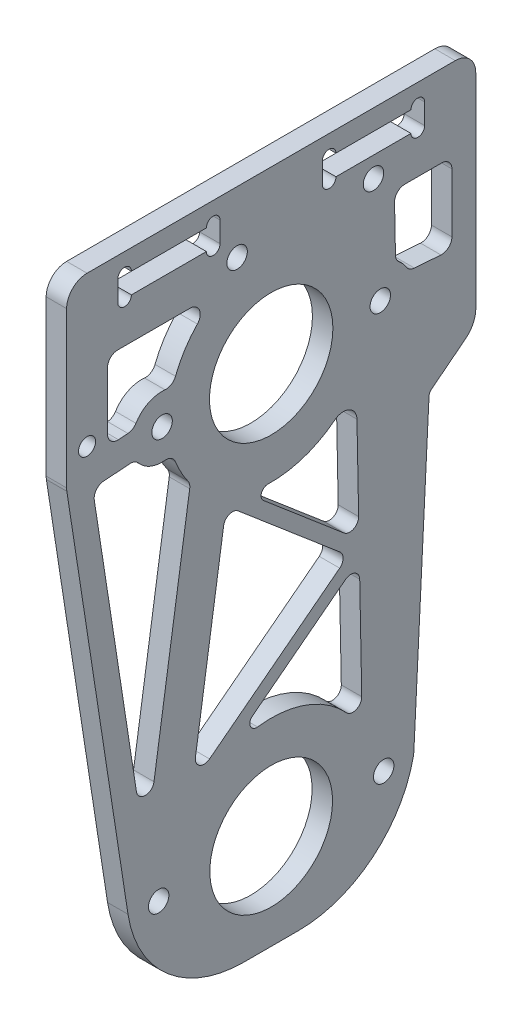
SolidWorks part; units mm, degrees
material "碳板"
ref_plane "前视基准面" through (0, 0, 0) normal (0, 0, 1) x (1, 0, 0)
ref_plane "上视基准面" through (0, 0, 0) normal (0, 1, 0) x (1, 0, 0)
ref_plane "右视基准面" through (0, 0, 0) normal (1, 0, 0) x (0, 0, -1)
sketch "草图1" plane through (0, 0, 0) normal (1, 0, 0) x (0, 0, -1)
  line L0 (-16, 26) -> (16, 26) construction
  line L1 (-30, 48) -> (30, 48)
  line L2 (-30, 48) -> (-30, -48)
  line L3 (-30, -48) -> (30, -48)
  line L4 (30, 48) -> (30, -48)
  line L5 (-30, 48) -> (30, -48) construction
  line L6 (-30, -48) -> (30, 48) construction
  line L7 (-16.5, -34) -> (16.5, -34) construction
  line L9 (-30, 48) -> (30, 48)
  line L10 (-30, 48) -> (-30, 51)
  line L11 (-30, 51) -> (30, 51)
  line L12 (30, 48) -> (30, 51)
  circle A0 centre (0, 26) radius 9.05
  circle A1 centre (0, -34) radius 9
  circle A2 centre (-16, 26) radius 1.5
  circle A3 centre (16, 26) radius 1.5
  circle A4 centre (-16.5, -34) radius 1.5
  circle A5 centre (16.5, -34) radius 1.5
  point P0 (0, 0)
  point P12 (0, 26)
  point P17 (0, -34)
  dimension "D2" = 18.1
  dimension "D3" = 18
  dimension "D4" = 60
  dimension "D5" = 22
  dimension "D6" = 14
  dimension "D7" = 3
  dimension "D9" = 33
  dimension "D1" = 60
  dimension "D8" = 32
  dimension "D10" = 3
extrude "凸台-拉伸1" add sketch "草图1" along normal blind 3 contours L4 L1 L2 L3 A5 A4 A3 A2 A1 A0 | L1 L12 L11 L10 region at (0, 49.5, 0) region at (0, 0.3975, 0)
sketch "草图2" plane through (3, 0, 0) normal (1, 0, 0) x (0, 0, -1)
  line L0 (-30, 51) -> (30, 51) construction
  line L1 (-30, 25) -> (-21, -33.4185)
  line L2 (30, 51) -> (30, -48) construction
  line L4 (0, 51) -> (0, -48) construction
  line L6 (-30, 25) -> (-30, -48)
  line L7 (-30, -48) -> (30, -48)
  line L8 (30, -48) -> (30, 25)
  line L9 (-30, -48) -> (-4, -48)
  line L10 (30, 25) -> (30, -48)
  line L11 (30, 25) -> (21, -33.4185)
  line L12 (30, -48) -> (4, -48)
  arc A2 (-21, -33.4185) -> (-4, -48) centre (-4, -30.7994) ccw
  arc A3 (21, -33.4185) -> (4, -48) centre (4, -30.7994) cw
  dimension "D1" = 26
  dimension "D2" = 4
  dimension "D3" = 9
extrude "切除-拉伸1" cut sketch "草图2" against normal through all contours A2 L1 | L11 A3 region at (3, -25.7143, -25.2603) region at (3, -25.7143, 25.2603)
sketch "草图3" plane through (3, 0, 0) normal (1, 0, 0) x (0, 0, -1)
  line L0 (-30, 51) -> (-30, 25) construction
  line L8 (-22.5, 48) -> (-22.5, 45)
  line L9 (-22.5, 45) -> (-7.5, 45)
  line L10 (-7.5, 45) -> (-7.5, 48)
  line L11 (-7.5, 48) -> (-22.5, 48)
  line L12 (7.5, 48) -> (7.5, 45)
  line L13 (7.5, 45) -> (22.5, 45)
  line L14 (22.5, 45) -> (22.5, 48)
  line L15 (22.5, 48) -> (7.5, 48)
  line L17 (-30, 51) -> (30, 51) construction
  circle A0 centre (-27, 29) radius 1.25
  circle A2 centre (15, 42) radius 1.5
  circle A4 centre (-5, 42) radius 1.5
  dimension "D6" = 2.5
  dimension "D7" = 3
  dimension "D8" = 3
  dimension "D9" = 20
  dimension "D10" = 2.5
  dimension "D11" = 3
  dimension "D12" = 16
  dimension "D1" = 7.5
  dimension "D2" = 22.5
  dimension "D3" = 37.5
  dimension "D4" = 3
  dimension "D5" = 3
extrude "切除-拉伸2" cut sketch "草图3" against normal through all
sketch "草图4" plane through (3, 0, 0) normal (1, 0, 0) x (0, 0, -1)
  line L0 (0, 51) -> (0, 16.95) construction
  line L1 (-30, 51) -> (30, 51) construction
  line L2 (-7.5, 48) -> (-22.5, 48) construction
  line L3 (-22.5, 48) -> (-22.5, 45) construction
  line L4 (-22.5, 45) -> (-7.5, 45) construction
  line L5 (-7.5, 45) -> (-7.5, 48) construction
  circle A0 centre (-21.5, 48) radius 1
  circle A1 centre (-21.5, 45) radius 1
  circle A2 centre (-8.5, 48) radius 1
  circle A3 centre (-8.5, 45) radius 1
  circle A4 centre (0, 26) radius 9.05 construction
  circle A5 centre (8.5, 45) radius 1
  circle A6 centre (8.5, 48) radius 1
  circle A7 centre (21.5, 45) radius 1
  circle A8 centre (21.5, 48) radius 1
  dimension "D1" = 2
extrude "切除-拉伸3" cut sketch "草图4" against normal through all
sketch "草图6" plane through (3, 0, 0) normal (1, 0, 0) x (0, 0, -1)
  line L0 (-16.5, -34) -> (-5, 42) construction
  line L1 (15, 42) -> (16.5, -34) construction
  line L2 (12.0006, 41.9408) -> (13.5006, -34.0592)
  line L3 (-13.5338, -34.4488) -> (-2.0338, 41.5512)
  line L4 (17.9994, 42.0592) -> (19.4994, -33.9408)
  line L5 (-19.4662, -33.5512) -> (-7.9662, 42.4488)
  line L6 (30, 51) -> (30, 25) construction
  line L7 (30, 25) -> (21, -33.4185) construction
  line L8 (-30, 51) -> (-30, 25) construction
  line L9 (-30, 25) -> (-21, -33.4185) construction
  line L10 (-37.8642, 39) -> (39.1637, 39)
  line L11 (-11.8122, -23.0714) -> (12.9081, -4.0406) construction
  line L12 (12.9081, -4.0406) -> (-6.4448, 12.3998) construction
  line L13 (-12.3921, -24.7799) -> (14.4977, -4.0789)
  line L14 (30, 51) -> (30, 25) construction
  line L15 (30, 25) -> (21, -33.4185) construction
  line L16 (-30, 51) -> (-30, 25) construction
  line L17 (-30, 25) -> (-21, -33.4185) construction
  line L19 (-26.5, 25.268) -> (-17.5408, -32.8855)
  line L20 (33.5, 51) -> (33.5, 24.732)
  line L21 (33.5, 24.732) -> (24.4592, -33.9514)
  line L22 (-33.5, 51) -> (-33.5, 24.732)
  line L23 (-33.5, 24.732) -> (-24.4592, -33.9514)
  line L24 (26.5, 51) -> (26.5, 25.268)
  line L25 (26.5, 25.268) -> (17.5408, -32.8855)
  line L26 (-26.5, 51) -> (-33.5, 51)
  line L27 (-17.5408, -32.8855) -> (-24.4592, -33.9514)
  line L28 (33.5, 51) -> (26.5, 51)
  line L29 (24.4592, -33.9514) -> (17.5408, -32.8855)
  line L30 (-16, 26) -> (-30, 25) construction
  line L31 (16, 26) -> (30, 25) construction
  line L32 (-5, 42) -> (-30, 42) construction
  line L33 (15, 42) -> (30, 42) construction
  line L34 (15, 40) -> (30, 40)
  line L35 (15.8575, 24.0051) -> (29.8575, 23.0051)
  line L36 (-16.1425, 27.9949) -> (-30.1425, 26.9949)
  line L37 (-5, 44) -> (-30, 44)
  line L38 (15, 44) -> (30, 44)
  line L39 (16.1425, 27.9949) -> (30.1425, 26.9949)
  line L40 (-15.8575, 24.0051) -> (-29.8575, 23.0051)
  line L41 (-5, 40) -> (-30, 40)
  line L42 (15, 40) -> (15, 44)
  line L43 (30, 40) -> (30, 44)
  line L44 (15.8575, 24.0051) -> (16.1425, 27.9949)
  line L45 (29.8575, 23.0051) -> (30.1425, 26.9949)
  line L46 (-16.1425, 27.9949) -> (-15.8575, 24.0051)
  line L47 (-30.1425, 26.9949) -> (-29.8575, 23.0051)
  line L48 (-5, 44) -> (-5, 40)
  line L49 (-30, 44) -> (-30, 40)
  line L50 (14.4977, -4.0789) -> (-5.7974, 13.1619)
  line L51 (-13.6121, -23.1951) -> (11.3185, -4.0024)
  line L52 (11.3185, -4.0024) -> (-7.0923, 11.6376)
  line L53 (-13.0021, -23.9875) -> (12.9081, -4.0406) construction
  line L54 (-26.5, 51) -> (-26.5, 25.268) construction
  line L55 (-24, 25.4286) -> (-24, 54.0508)
  arc A10 (15.05, 26) -> (15.05, 26) centre (0, 26) ccw
  circle A11 centre (0, 26) radius 15.05
  arc A12 (12.0006, 41.9408) -> (17.9994, 42.0592) centre (15, 42) cw
  circle A13 centre (0, -34) radius 15
  circle A14 centre (0, -34) radius 15
  arc A15 (13.5006, -34.0592) -> (19.4994, -33.9408) centre (16.5, -34) ccw
  arc A16 (-13.5338, -34.4488) -> (-19.4662, -33.5512) centre (-16.5, -34) cw
  arc A17 (-2.0338, 41.5512) -> (-7.9662, 42.4488) centre (-5, 42) ccw
  circle A20 centre (-16, 26) radius 4.5
  circle A21 centre (-16, 26) radius 4.5
  circle A25 centre (16, 26) radius 4.5
  circle A26 centre (16, 26) radius 4.5
  dimension "D11" = 1
  dimension "D12" = 1
  dimension "D14" = 6
  dimension "D1" = 6
  dimension "D2" = 6
  dimension "D3" = 3
  dimension "D4" = 3
  dimension "D5" = 3
  dimension "D6" = 3
  dimension "D7" = 3.5
  dimension "D8" = 3.5
  dimension "D9" = 2
  dimension "D10" = 2
  dimension "D13" = 1
extrude "切除-拉伸4" cut sketch "草图6" against normal blind 10 contours A21 L40 L19 L5 A11 | L51 L52 L3 | A14 L2 L13 | A11 L50 L2 | A26 L39 L24 L10 L4 | A21 A11 L5 L10 L36 | A11 L10 L5 region at (3, 33.422, -22.4591) region at (3, 38.7905, 8.223) region at (3, 7.6235, -7.7996) region at (3, -4.8028, 2.2994) region at (3, 5.7262, 18.7951) region at (3, 34.3826, 18.2454) region at (3, -15.8344, -7.5191)
sketch "草图7" plane through (3, 0, 0) normal (1, 0, 0) x (0, 0, -1)
  line L0 (28.4391, 14.8685) -> (23.1704, 10.7521)
  line L1 (30, 25) -> (21, -33.4185) construction
  line L2 (23.1704, 10.7521) -> (24.7277, -9.2221)
  line L3 (24.7277, -9.2221) -> (28.4391, 14.8685)
  line L4 (-30, 51) -> (30, 51) construction
  circle A0 centre (0, -34) radius 9 construction
  dimension "D1" = 38
  dimension "D2" = 21
extrude "切除-拉伸5" cut sketch "草图7" against normal through all
sketch "草图8" plane through (3, 0, 0) normal (1, 0, 0) x (0, 0, -1)
  line L0 (28.4391, 14.8685) -> (30.0151, 16.0998)
  line L1 (30.0151, 16.0998) -> (30, 25)
  line L2 (30, 25) -> (28.4391, 14.8685) construction
  line L3 (30, 25) -> (28.4391, 14.8685)
  line L4 (28.4391, 14.8685) -> (23.1704, 10.7521) construction
  dimension "D1" = 2
extrude "凸台-拉伸2" add sketch "草图8" against normal up to surface (3 mm away) up to face at (0, 7.9107, -7.5294)
fillet "圆角1" radius 1.3 7 edges at (1.5, -27.19, -13.365) (1.5, -26.9103, 18.4614) (1.5, -21.643, 11.596) (1.5, -2.7061, -12.8818) (1.5, -5.2838, -12.9326) (1.5, -4.0024, -11.3185) (1.5, 11.2371, 6.6208)
fillet "圆角9" radius 2 1 edges at (1.5, 17.5903, -12.4812)
fillet "圆角3" radius 3 3 edges at (1.5, 51, -30) (1.5, 25, 30) (1.5, 51, 30)
fillet "圆角4" radius 1.5 14 edges at (1.5, 21.7771, 14.4454) (1.5, 23.2669, 26.1917) (1.5, 23.7179, 19.8784) (1.5, 27.7077, 20.1634) (1.5, 30.2229, 14.4454) (1.5, 39, -18.0598) (1.5, 39, -26.5) (1.5, 27.2551, -26.5) (1.5, 27.7077, -20.1634) (1.5, 29.9033, -18.2393) (1.5, 16.7318, 11.8576) (1.5, 39, 7.583) (1.5, 39, 24) (1.5, 27.4337, 24)
fillet "圆角5" radius 4 1 edges at (1.5, 16.0998, -30.0151)
sketch "草图9" plane through (3, 0, 0) normal (1, 0, 0) x (0, 0, -1)
  line L0 (23.1704, 10.7521) -> (20.9104, -34)
  line L1 (24.7277, -9.2221) -> (21, -33.4185) construction
  line L2 (23.1704, 10.7521) -> (24.7277, -9.2221)
  line L3 (24.7277, -9.2221) -> (20.9104, -34)
  point P8 (16.5, -34)
extrude "切除-拉伸6" cut sketch "草图9" against normal through all
fillet "圆角6" radius 1 3 edges at (1.5, 10.7521, -23.1704) (1.5, -20.9974, 7.4787) (1.5, 11.4256, 3.7535)
fillet "圆角10" radius 5 1 edges at (1.5, -33.925, -20.9142)
